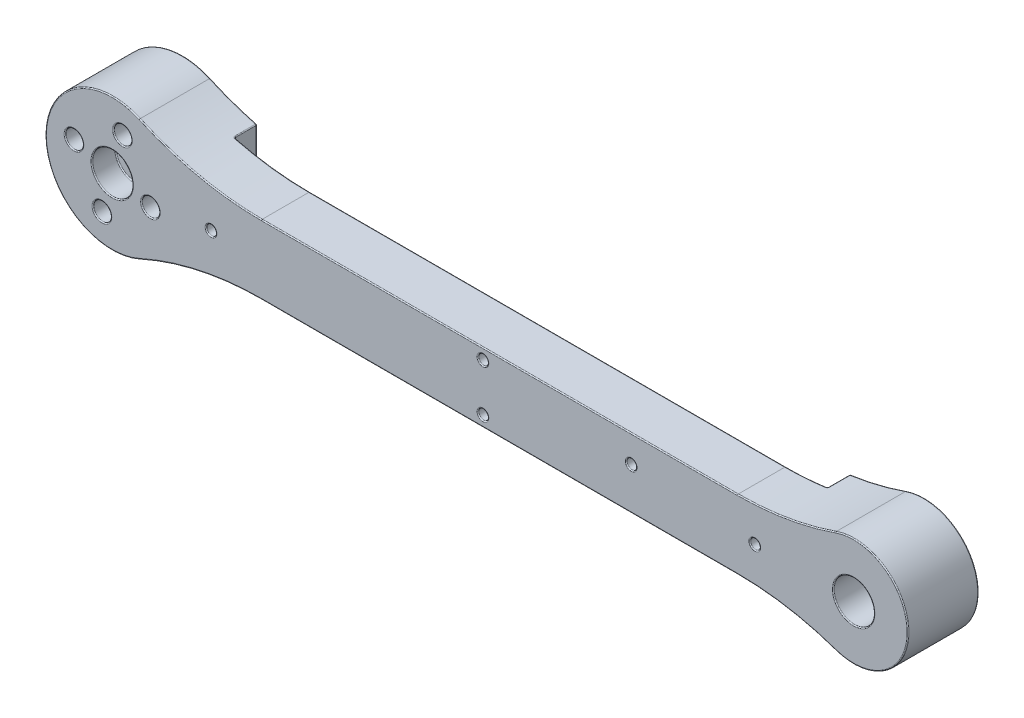
SolidWorks part; units mm, degrees
ref_plane "정면" through (0, 0, 0) normal (0, 0, 1) x (1, 0, 0)
ref_plane "윗면" through (0, 0, 0) normal (0, 1, 0) x (1, 0, 0)
ref_plane "우측면" through (0, 0, 0) normal (1, 0, 0) x (0, 0, -1)
sketch "스케치1" plane through (0, 0, 0) normal (0, 0, 1) x (1, 0, 0)
  line L0 (0, 11) -> (50, 11)
  line L1 (50, 11) -> (50, -11)
  line L2 (50, -11) -> (0, -11)
  line L3 (0, 0) -> (78.6227, 0) construction
  line L4 (8.4853, 7) -> (50, 7)
  line L5 (8.4853, -7) -> (50, -7)
  line L6 (0, 0) -> (25.6752, -44.4707) construction
  line L7 (-2.0706, -7.7274) -> (0, 0) construction
  arc A0 (0, 11) -> (0, -11) centre (0, 0) ccw
  circle A1 centre (0, 0) radius 4.1
  circle A6 centre (0, 0) radius 11
  circle A7 centre (-2.0706, -7.7274) radius 1.8
  circle A8 centre (-7.7274, 2.0706) radius 1.8
  circle A9 centre (2.0706, 7.7274) radius 1.8
  circle A10 centre (7.7274, -2.0706) radius 1.8
  point P15 (0, 0)
  point P26 (0, 0)
  dimension "D1" = 22
  dimension "D2" = 3.6
  dimension "D4" = 8.2
  dimension "D3" = 8
  dimension "D6" = 50
  dimension "D7" = 14
  dimension "D8" = 60
  dimension "D5" = 45
  dimension "D9" = 4
extrude "보스-돌출1" add sketch "스케치1" along normal blind 14.3 contours A6 A0 A10 A9 A8 A7 A1 | A6 L5 L1 L4 region at (4.5578, 9.6684, 0) region at (30.0954, 0, 0)
sketch "스케치3" plane through (0, 0, 0) normal (0, 0, -1) x (-1, 0, 0)
  circle A0 centre (0, 0) radius 4.1
  circle A1 centre (0, 0) radius 2.45
  circle M6 centre (0, 0) radius 4.1
  dimension "D1" = 8.2
  dimension "D2" = 4.9
extrude "보스-돌출2" add sketch "스케치3" against normal blind 9.5 contours A1 M6 region at (3.984, 0, 0)
sketch "스케치4" plane through (0, 0, 0) normal (0, 0, -1) x (-1, 0, 0)
  line L3 (-8.4853, 7) -> (-50, 7)
  line L4 (-50, 7) -> (-50, -7)
  line L5 (-50, -7) -> (-8.4853, -7)
  line L6 (-8.4853, 7) -> (-50, 7)
  line L7 (-50, 7) -> (-50, -7)
  line L8 (-50, -7) -> (-8.4853, -7)
  arc A0 (-5.0706, 7.7274) -> (0.9294, 7.7274) centre (-2.0706, 7.7274) ccw
  circle A1 centre (-7.7274, -2.0706) radius 1.8
  circle A2 centre (-7.7274, -2.0706) radius 1.8
  circle A3 centre (-2.0706, 7.7274) radius 1.8
  circle A4 centre (-2.0706, 7.7274) radius 1.8
  circle A5 centre (7.7274, 2.0706) radius 1.8
  circle A6 centre (7.7274, 2.0706) radius 1.8
  circle A7 centre (2.0706, -7.7274) radius 1.8
  circle A8 centre (2.0706, -7.7274) radius 1.8
  circle A9 centre (0, 0) radius 2.45
  circle A10 centre (0, 0) radius 2.45
  arc A11 (7.7274, 5.0706) -> (7.7274, -0.9294) centre (7.7274, 2.0706) ccw
  circle A12 centre (-7.7274, -2.0706) radius 3
  arc A13 (5.0706, -7.7274) -> (-0.9294, -7.7274) centre (2.0706, -7.7274) ccw
  circle A14 centre (0, 0) radius 13.5
  circle A15 centre (-2.0706, 7.7274) radius 3
  circle A16 centre (7.7274, 2.0706) radius 3
  arc A17 (-8.4853, -7) -> (-8.4853, 7) centre (0, 0) ccw
  circle A18 centre (2.0706, -7.7274) radius 3
  circle M9 centre (-7.7274, -2.0706) radius 1.8
  circle M10 centre (-2.0706, 7.7274) radius 1.8
  circle M11 centre (7.7274, 2.0706) radius 1.8
  circle M12 centre (2.0706, -7.7274) radius 1.8
  dimension "D6" = 6
  dimension "D8" = 27
  dimension "D1" = 0
  dimension "D2" = 0
  dimension "D3" = 0
  dimension "D4" = 0
  dimension "D5" = 0
  dimension "D7" = 0
sketch "스케치5" plane through (0, 0, 0) normal (0, 0, -1) x (-1, 0, 0)
  line L0 (-50, 7) -> (-141.5147, 7)
  line L1 (-50, -7) -> (-141.5147, -7)
  line L2 (-50, 7) -> (-50, -7)
  circle A0 centre (-150, 0) radius 11
  circle A1 centre (-150, 0) radius 4.8
  circle A2 centre (-150, 0) radius 4.1
  line M23 (-50, 7) -> (-50, -7)
  dimension "D1" = 22
  dimension "D2" = 9.6
  dimension "D3" = 8.2
  dimension "D4" = 150
extrude "보스-돌출3" add sketch "스케치5" against normal up to surface (14.3 mm away) contours A0 L1 L0 M23 | A0 A1 | A1 A2 region at (94.9009, 0, 0) region at (139.9406, 3.6138, 0) region at (154.6642, 0, 0) up to face at (9.5274, -2.0706, 14.3)
extrude "컷-돌출6" cut sketch "스케치5<3>" against normal blind 1.8 contours A1 A2 region at (154.6642, 0, 0)
sketch "스케치5<3>" plane through (0, 0, 0) normal (0, 0, -1) x (-1, 0, 0) same geometry as "스케치5"
sketch "스케치6" plane through (0, 0, 0) normal (0, 0, -1) x (-1, 0, 0)
  line L0 (0, 0) -> (-78.6227, 0) construction
  line L1 (-135, -7) -> (-15, -7)
  line L2 (-135, -7) -> (-135, 7)
  line L3 (-135, 7) -> (-15, 7)
  line L4 (-15, -7) -> (-15, 7)
  line L5 (-135, -7) -> (-15, 7) construction
  line L6 (-135, 7) -> (-15, -7) construction
  line L7 (-125.1, 2.6) -> (-24.9, 2.6)
  line L8 (-125.1, 2.6) -> (-125.1, -2.6)
  line L9 (-125.1, -2.6) -> (-24.9, -2.6)
  line L10 (-24.9, 2.6) -> (-24.9, -2.6)
  line L11 (-125.1, 2.6) -> (-24.9, -2.6) construction
  line L12 (-125.1, -2.6) -> (-24.9, 2.6) construction
  circle A0 centre (-130, 0) radius 1
  circle A1 centre (-75, 4.8) radius 1
  circle A2 centre (-75, -4.8) radius 1
  circle A3 centre (-20, 0) radius 1
  point P0 (-75, 0)
  point P5 (-75, 0)
  line M29 (-8.4853, 7) -> (-141.5147, 7)
  line M31 (-141.5147, -7) -> (-8.4853, -7)
  dimension "D6" = 2
  dimension "D7" = 2
  dimension "D10" = 2
  dimension "D12" = 2
  dimension "D1" = 75
  dimension "D2" = 14
  dimension "D3" = 120
  dimension "D4" = 100.2
  dimension "D5" = 5.2
  dimension "D8" = 2.2
  dimension "D9" = 2.2
  dimension "D11" = 5
  dimension "D13" = 5
extrude "컷-돌출7" cut sketch "스케치6" against normal blind 4.55 contours L4 L2 A3 A2 A1 A0 L7 L10 L9 L8 M31 M29 | L10 L7 L8 L9 | A0 | A1 | A2 | A3 region at (133.7919, 0, 0) region at (75, 0, 0) region at (130, 0, 0) region at (75, 4.8, 0) region at (75, -4.8, 0) region at (20, 0, 0)
extrude "컷-돌출8" cut sketch "스케치6<3>" against normal blind 5.2 from surface contours L7 L10 L9 L8 starting at face at (75, 0, 4.55)
sketch "스케치6<3>" plane through (0, 0, 0) normal (0, 0, -1) x (-1, 0, 0) same geometry as "스케치6"
extrude "컷-돌출9" cut sketch "스케치6<4>" against normal through all contours A0 | A1 | A2 | A3
sketch "스케치6<4>" plane through (0, 0, 0) normal (0, 0, -1) x (-1, 0, 0) same geometry as "스케치6"
sketch "스케치9" plane through (0, 0, 0) normal (0, 0, -1) x (-1, 0, 0)
  line L0 (-110, 7) -> (-110, -7) construction
  line L1 (-50, 7) -> (-141.5147, 7) construction
  line L2 (-50, -7) -> (-141.5147, -7) construction
  circle A0 centre (-105, 1.5) radius 1
  dimension "D1" = 2
  dimension "D2" = 40
  dimension "D3" = 5
  dimension "D4" = 5.5
extrude "컷-돌출10" cut sketch "스케치9" against normal through all
sketch "스케치10" plane through (0, 0, 0) normal (0, 0, -1) x (-1, 0, 0)
  circle A0 centre (0, 0) radius 13.5
  circle A1 centre (0, 0) radius 11
  dimension "D1" = 27
extrude "보스-돌출4" add sketch "스케치10" against normal up to surface (14.3 mm away) from surface up to face at (104, 1.5, 14.3) starting at face at (9.5274, -2.0706, 0)
extrude "컷-돌출11" cut sketch "스케치4" against normal blind 5 from surface contours A0 A15 M10 | A16 A11 M11 | A12 M9 | A13 A18 M12 region at (-0.2959, -10.0401, 0) region at (-10.6176, 2.4511, 0) region at (0.2959, 10.0401, 0) region at (10.6426, -2.0706, 0) starting at face at (7.0108, 0, 0)
fillet "필렛1" radius 60 4 edges at (11.5434, 7, 7.15) (11.5434, -7, 7.15) (141.5147, -7, 7.15) (141.5147, 7, 7.15)
fillet "필렛2" radius 0.2 65 edges at (135, 7.6044, 2.275) (15, 8.9625, 2.275) (15, -8.9625, 2.275) (135, -7.6044, 2.275) (-0.2706, -7.7274, 5) (0.9294, -7.7274, 5) (9.5274, -2.0706, 5) (10.7274, -2.0706, 5) (-5.9274, 2.0706, 5) (-4.7274, 2.0706, 5) (3.8706, 7.7274, 5) (5.0706, 7.7274, 5) (145.2, 0, 1.8) (145.9, 0, 1.8) (-4.1, 0, 9.5) (-2.45, 0, 9.5) (9.5274, -2.0706, 14.3) (3.8706, 7.7274, 14.3) (-5.9274, 2.0706, 14.3) (-0.2706, -7.7274, 14.3) (4.1, 0, 14.3) (154.1, 0, 14.3) (19, 0, 14.3) (74, -4.8, 14.3) (74, 4.8, 14.3) (129, 0, 14.3) (104, 1.5, 14.3) (136.5755, 7.8511, 14.3) (161, 0, 14.3) (136.5755, -7.8511, 14.3) (78.3627, -7, 14.3) (17.6032, -8.3415, 14.3) (-13.5, 0, 14.3) (17.6032, 8.3415, 14.3) (78.3627, 7, 14.3) (-4.7274, 2.0706, 0) (0.9294, -7.7274, 0) (-2.45, 0, 0) (10.2054, 10.4366, 0) (-13.5, 0, 0) (10.2054, -10.4366, 0) (15, 0, 0) (5.0706, 7.7274, 0) (10.7274, -2.0706, 0) (125.1, 0, 4.55) (75, -2.6, 4.55) (24.9, 0, 4.55) (75, 2.6, 4.55) (130.7634, 7.1513, 4.55) (78.3627, 7, 4.55) (22.547, 7.4926, 4.55) (15, 0, 4.55) (22.547, -7.4926, 4.55) (78.3627, -7, 4.55) (130.7634, -7.1513, 4.55) (135, 0, 4.55) (19, 0, 4.55) (74, -4.8, 4.55) (74, 4.8, 4.55) (129, 0, 4.55) (140.7478, -8.7149, 0) (161, 0, 0) (140.7478, 8.7149, 0) (135, 0, 0) (145.2, 0, 0)
